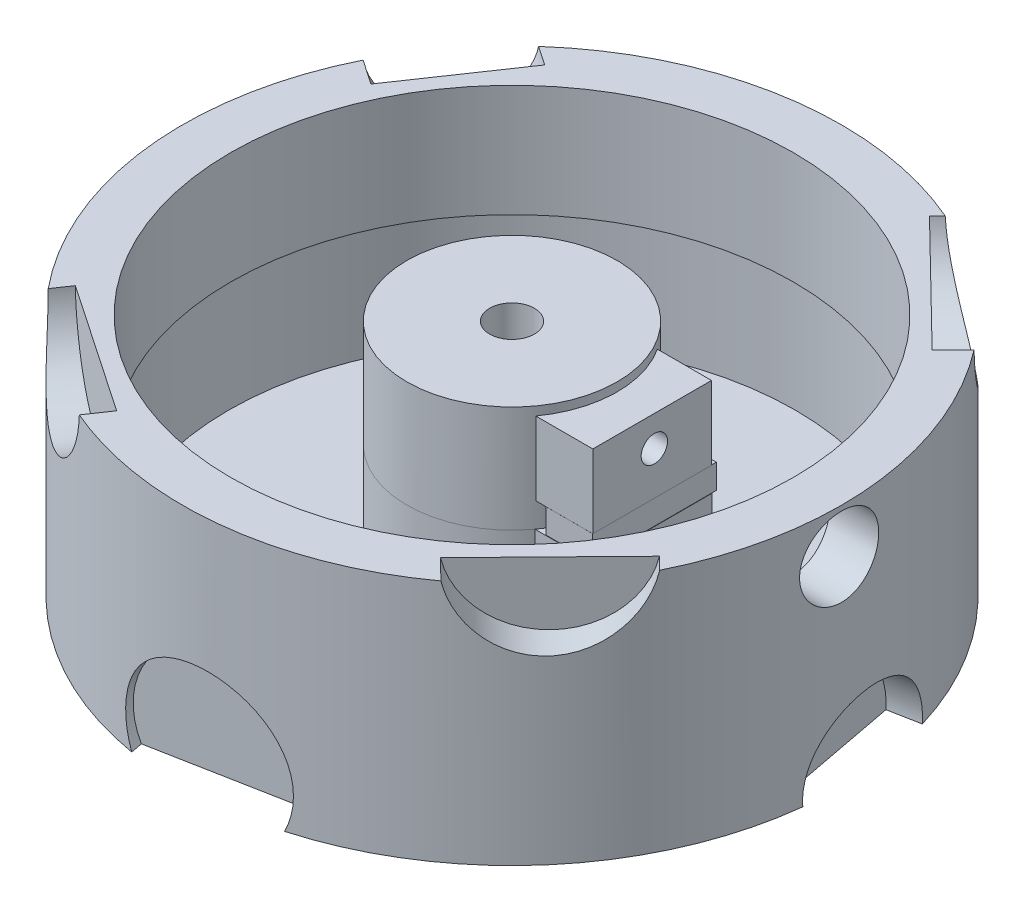
SolidWorks part; units mm, degrees
ref_plane "Front Plane" through (0, 0, 0) normal (0, 0, 1) x (1, 0, 0)
ref_plane "Top Plane" through (0, 0, 0) normal (0, 1, 0) x (1, 0, 0)
ref_plane "Right Plane" through (0, 0, 0) normal (1, 0, 0) x (0, 0, -1)
sketch "Sketch1" plane through (0, 0, 0) normal (0, 1, 0) x (1, 0, 0)
  circle A0 centre (0, 0) radius 15.958
extrude "ShaftHolderNearMotor" add sketch "Sketch1" along normal blind 17.19
sketch "Sketch2" plane through (0, 17.19, 0) normal (0, 1, 0) x (1, 0, 0)
  circle A0 centre (0, 0) radius 3.4
extrude "Cut-Extrude1" cut sketch "Sketch2" against normal blind 16.85 contours A0
ref_plane "Plane1" through (0, 12.15, 0) normal (0, 1, 0) x (1, 0, 0)
ref_axis "Axis1" through (0, 0.34, 0) along (0, 1, 0)
ref_point "Point2"
sketch "Sketch5" plane through (0, 12.15, 0) normal (0, 1, 0) x (1, 0, 0)
  line L0 (0, 0) -> (2.6, 0) construction
  line L2 (2.6, -3.5716) -> (4.1507, -3.5716)
  line L3 (2.6, -3.5716) -> (2.6, 3.6126)
  line L4 (2.6, 3.6126) -> (4.1507, 3.6126)
  line L5 (4.1507, -3.5716) -> (4.1507, 3.6126)
extrude "Boss-Extrude2" add sketch "Sketch5" against normal blind 13.55
sketch "Sketch7" plane through (2.6, 0, 0) normal (-1, 0, 0) x (0, 0, 1)
  line L1 (-8.6717, 14.8677) -> (9.3323, 14.8677)
  line L2 (-8.6717, 14.8677) -> (-8.6717, 3.7227)
  line L3 (-8.6717, 3.7227) -> (9.3323, 3.7227)
  line L4 (9.3323, 14.8677) -> (9.3323, 3.7227)
extrude "Boss-Extrude3" add sketch "Sketch7" against normal blind 19
sketch "Sketch6" plane through (2.6, 0, 0) normal (-1, 0, 0) x (0, 0, 1)
  line L1 (-2.1909, 0.34) -> (-2.1909, 14.8677) construction
  line L2 (2.1909, 14.8677) -> (2.1909, 0.34) construction
  line L3 (-2.1909, 15.4522) -> (2.1909, 15.4522) construction
  circle A0 centre (0, 10.2369) radius 2
extrude "Cut-Extrude2" cut sketch "Sketch6" against normal up to surface (19 mm away) and the other way blind 1 up to face at (21.6, 9.2952, 0.3303)
ref_axis "Axis2" through (-1.8994, 10.2369, 0) along (-1, 0, 0)
ref_axis "Axis4" through (21.6, 10.2369, 0) along (-1, 0, 0)
ref_plane "Plane3" through (0, 0, 0) normal (0, 0, 1) x (1, 0, 0)
sketch "Sketch9" plane through (0, 0, 0) normal (0, 0, 1) x (1, 0, 0)
  line L0 (11.8765, 10.2369) -> (11.8765, 5.8619) construction
  line L1 (4.9434, 5.8619) -> (11.8765, 5.8619) construction
  line L2 (4.9434, 5.8619) -> (4.9434, 10.2369) construction
  line L3 (4.9434, 10.2369) -> (4.9434, 14.6143) construction
  line L4 (4.9434, 14.6143) -> (11.8765, 14.6143) construction
  line L5 (11.8765, 14.6143) -> (11.8765, 10.2369) construction
  line L6 (21.6, 10.2369) -> (2.6, 10.2369) construction
  line L7 (4.9434, 14.6143) -> (11.8765, 5.8619) construction
  line L8 (4.9434, 14.6143) -> (2.3367, 17.9051) construction
  line L9 (11.8765, 5.8619) -> (13.8203, 3.408) construction
  line L11 (4.652, 14.9822) -> (8.7666, 14.9822)
  line L12 (4.652, 14.9822) -> (4.652, 5.4889)
  line L13 (4.652, 5.4889) -> (8.7666, 5.4889)
  line L14 (8.7666, 14.9822) -> (8.7666, 5.4889)
  circle A0 centre (4.9434, 14.6143) radius 0.4693 construction
  circle A1 centre (11.8765, 5.8619) radius 0.4759 construction
extrude "NutOpening" cut sketch "Sketch9" against normal blind 30 and the other way blind 5.31
sketch "Sketch10" plane through (0, 0, 0) normal (0, -1, 0) x (1, 0, 0)
  circle A0 centre (0, 0) radius 50
extrude "Boss-Extrude4" add sketch "Sketch10" along normal blind 20
sketch "Sketch11" plane through (0, 0, 0) normal (0, 1, 0) x (1, 0, 0)
  line L1 (31.7817, 38.8528) -> (14.4942, 48.0577) construction
  line L2 (14.4942, 48.0577) -> (-5, 49.9462) construction
  line L3 (-5, 49.9462) -> (-23.733, 44.2308) construction
  line L4 (-23.733, 44.2308) -> (-38.8528, 31.7817) construction
  line L5 (-38.8528, 31.7817) -> (-48.0577, 14.4942) construction
  line L6 (-48.0577, 14.4942) -> (-49.9462, -5) construction
  line L7 (-49.9462, -5) -> (-44.2308, -23.733) construction
  line L8 (-44.2308, -23.733) -> (-31.7817, -38.8528) construction
  line L9 (-31.7817, -38.8528) -> (-14.4942, -48.0577) construction
  line L10 (-14.4942, -48.0577) -> (5, -49.9462) construction
  line L11 (5, -49.9462) -> (23.733, -44.2308) construction
  line L12 (23.733, -44.2308) -> (38.8528, -31.7817) construction
  line L13 (38.8528, -31.7817) -> (48.0577, -14.4942) construction
  line L14 (48.0577, -14.4942) -> (49.9462, 5) construction
  line L15 (49.9462, 5) -> (44.2308, 23.733) construction
  line L16 (44.2308, 23.733) -> (31.7817, 38.8528) construction
  circle A0 centre (0, 0) radius 49.2313 construction
  circle A1 centre (5, -49.9462) radius 5
  circle A2 centre (-14.4942, -48.0577) radius 5
  circle A3 centre (-31.7817, -38.8528) radius 5
  circle A4 centre (-44.2308, -23.733) radius 5
  circle A5 centre (-49.9462, -5) radius 5
  circle A6 centre (-48.0577, 14.4942) radius 5
  circle A7 centre (-38.8528, 31.7817) radius 5
  circle A8 centre (-23.733, 44.2308) radius 5
  circle A9 centre (-5, 49.9462) radius 5
  circle A10 centre (14.4942, 48.0577) radius 5
  circle A11 centre (31.7817, 38.8528) radius 5
  circle A12 centre (44.2308, 23.733) radius 5
  circle A13 centre (49.9462, 5) radius 5
  circle A14 centre (48.0577, -14.4942) radius 5
  circle A15 centre (38.8528, -31.7817) radius 5
  circle A16 centre (23.733, -44.2308) radius 5
sketch "Sketch12" plane through (0, 0, 0) normal (0, 1, 0) x (1, 0, 0)
  circle A0 centre (0, 0) radius 43
  circle A1 centre (0, 0) radius 15.9579
extrude "CutToRemveExcessMaterial" cut sketch "Sketch12" against normal offset from surface (17 mm away) 3 up to face at (0, -20, -50)
sketch "Sketch13" plane through (0, 0, 0) normal (0, 1, 0) x (1, 0, 0)
  circle A0 centre (0, 0) radius 42.6967
  circle A1 centre (0, 0) radius 50
extrude "Boss-Extrude5" add sketch "Sketch13" along normal blind 17
sketch "Sketch14" plane through (8.7666, 0, 0) normal (-1, 0, 0) x (0, 0, 1)
  line L1 (-5.4541, 10.2369) -> (-2.7271, 5.5135)
  line L2 (-2.7271, 5.5135) -> (2.7271, 5.5135)
  line L3 (2.7271, 5.5135) -> (5.4541, 10.2369)
  line L4 (5.4541, 10.2369) -> (2.7271, 14.9603)
  line L5 (2.7271, 14.9603) -> (-2.7271, 14.9603)
  line L6 (-2.7271, 14.9603) -> (-5.4541, 10.2369)
  circle A0 centre (0, 10.2369) radius 4.7234 construction
extrude "Cut-Extrude6" cut sketch "Sketch14" along normal up to surface (4.1146 mm away) up to face at (4.652, 10.2369, -2)
sketch "Sketch16" plane through (21.6, 0, 0) normal (1, 0, 0) x (0, 0, -1)
  circle A0 centre (0, 10.2369) radius 6
extrude "Cut-Extrude7" cut sketch "Sketch16" along normal blind 40
ref_plane "Plane4" through (-0.571, 0, -49.9967) normal (-0.0114, 0, -0.9999) x (-0.9999, 0, 0.0114)
ref_plane "Plane5" through (-27.4359, 0, -41.8004) normal (-0.5487, 0, -0.836) x (-0.836, 0, 0.5487)
sketch "Sketch17" plane through (-0.571, 0, -49.9967) normal (-0.0114, 0, -0.9999) x (-0.9999, 0, 0.0114)
  line L1 (-6.9779, 26.3682) -> (19.0025, 26.3682)
sketch "Sketch18" plane through (-27.4359, 0, -41.8004) normal (-0.5487, 0, -0.836) x (-0.836, 0, 0.5487)
  line L1 (2.3429, -8.8145) -> (-7.3736, -8.8145)
  line L2 (2.3429, -8.8145) -> (2.3429, -36.514)
  line L3 (2.3429, -36.514) -> (-7.3736, -36.514)
  line L4 (-7.3736, -8.8145) -> (-7.3736, -36.514)
ref_plane "Plane6" through (18.6054, 0, -46.4095) normal (0.3721, 0, -0.9282) x (-0.9282, 0, -0.3721)
ref_plane "Plane7" through (34.9493, 0, -35.7568) normal (0.699, 0, -0.7151) x (-0.7151, 0, -0.699)
ref_plane "Plane8" through (45.9725, 0, -19.6605) normal (0.9194, 0, -0.3932) x (-0.3932, 0, -0.9194)
ref_plane "Plane9" through (49.1178, 0, -9.3511) normal (0.9824, 0, -0.187) x (-0.187, 0, -0.9824)
ref_plane "Plane10" through (46.4095, 0, 18.6054) normal (0.9282, 0, 0.3721) x (0.3721, 0, -0.9282)
ref_plane "Plane11" through (35.7568, 0, 34.9493) normal (0.7151, 0, 0.699) x (0.699, 0, -0.7151)
ref_plane "Plane12" through (9.3511, 0, 49.1178) normal (0.187, 0, 0.9824) x (0.9824, 0, -0.187)
ref_plane "Plane13" through (-28.1193, 0, 41.3438) normal (-0.5624, 0, 0.8269) x (0.8269, 0, 0.5624)
ref_plane "Plane14" through (-49.1178, 0, 9.3511) normal (-0.9824, 0, 0.187) x (0.187, 0, 0.9824)
ref_plane "Plane15" through (-41.3438, 0, -28.1193) normal (-0.8269, 0, -0.5624) x (-0.5624, 0, 0.8269)
sketch "Sketch19" plane through (9.3511, 0, 49.1178) normal (0.187, 0, 0.9824) x (0.9824, 0, -0.187)
  circle A0 centre (-6.5538, -15.0444) radius 12
extrude "Cut-Extrude8" cut sketch "Sketch19" against normal blind 5
sketch "Sketch20" plane through (35.7568, 0, 34.9493) normal (0.7151, 0, 0.699) x (0.699, 0, -0.7151)
  circle A0 centre (3.5584, 19.4292) radius 12
extrude "Cut-Extrude9" cut sketch "Sketch20" against normal blind 5
sketch "Sketch21" plane through (49.1178, 0, -9.3511) normal (0.9824, 0, -0.187) x (-0.187, 0, -0.9824)
  circle A0 centre (-4.7912, -19.2219) radius 10
sketch "Sketch22" plane through (34.9493, 0, -35.7568) normal (0.699, 0, -0.7151) x (-0.7151, 0, -0.699)
  circle A0 centre (5.4277, 18.4908) radius 12.5535
extrude "Cut-Extrude10" cut sketch "Sketch22" against normal blind 5
extrude "Cut-Extrude11" cut sketch "Sketch21" against normal blind 5 contours A0
sketch "Sketch23" plane through (-0.571, 0, -49.9967) normal (-0.0114, 0, -0.9999) x (-0.9999, 0, 0.0114)
  circle A0 centre (4.5252, -20.0178) radius 11.9653
extrude "Cut-Extrude12" cut sketch "Sketch23" against normal blind 5
sketch "Sketch25" plane through (-41.3438, 0, -28.1193) normal (-0.8269, 0, -0.5624) x (-0.5624, 0, 0.8269)
  circle A0 centre (-2.6498, 18.6432) radius 9.6297
extrude "Cut-Extrude13" cut sketch "Sketch25" against normal blind 5
sketch "Sketch26" plane through (-49.1178, 0, 9.3511) normal (-0.9824, 0, 0.187) x (0.187, 0, 0.9824)
  circle A0 centre (-4.4977, -19.1264) radius 15.0124
extrude "Cut-Extrude14" cut sketch "Sketch26" against normal blind 5
sketch "Sketch27" plane through (-28.1193, 0, 41.3438) normal (-0.5624, 0, 0.8269) x (0.8269, 0, 0.5624)
  circle A0 centre (-2.2875, 17.6222) radius 11.8547
extrude "Cut-Extrude15" cut sketch "Sketch27" against normal blind 5
sketch "Sketch28" plane through (0, 0, 0) normal (0, -1, 0) x (1, 0, 0)
  line L1 (12.7613, 9.4042) -> (21.6, 9.4042)
  line L2 (12.7613, 9.4042) -> (12.7613, -8.7683)
  line L3 (12.7613, -8.7683) -> (21.6, -8.7683)
  line L4 (21.6, 9.4042) -> (21.6, -8.7683)
extrude "Boss-Extrude6" add sketch "Sketch28" along normal up to surface (17 mm away) up to face at (0, -17, -43)
sketch "Sketch29" plane through (0, 3.7227, 0) normal (0, -1, 0) x (1, 0, 0)
  line L1 (21.5487, 9.3378) -> (14.5231, 9.3378)
  line L2 (21.5487, 9.3378) -> (21.5487, -9.4483)
  line L3 (21.5487, -9.4483) -> (14.5231, -9.4483)
  line L4 (14.5231, 9.3378) -> (14.5231, -9.4483)
extrude "Boss-Extrude7" add sketch "Sketch29" along normal up to surface (3.7227 mm away) up to face at (18.0666, 0, 0.3352)
sketch "Sketch30" plane through (0, 17.19, 0) normal (0, 1, 0) x (1, 0, 0)
  circle A0 centre (0, 0) radius 3.4
  circle A1 centre (0, 0) radius 8.7876
sketch "Sketch31" plane through (0, 17.19, 0) normal (0, 1, 0) x (1, 0, 0)
  circle A0 centre (0, 0) radius 26.3365
ref_point "Point3"
extrude "Cut-Extrude16" cut sketch "Sketch31" against normal blind 1
sketch "Sketch32" plane through (0, 14.8677, 0) normal (0, 1, 0) x (1, 0, 0)
  circle A0 centre (0, 0) radius 3.3803
extrude "Cut-Extrude17" cut sketch "Sketch32" against normal blind 2
